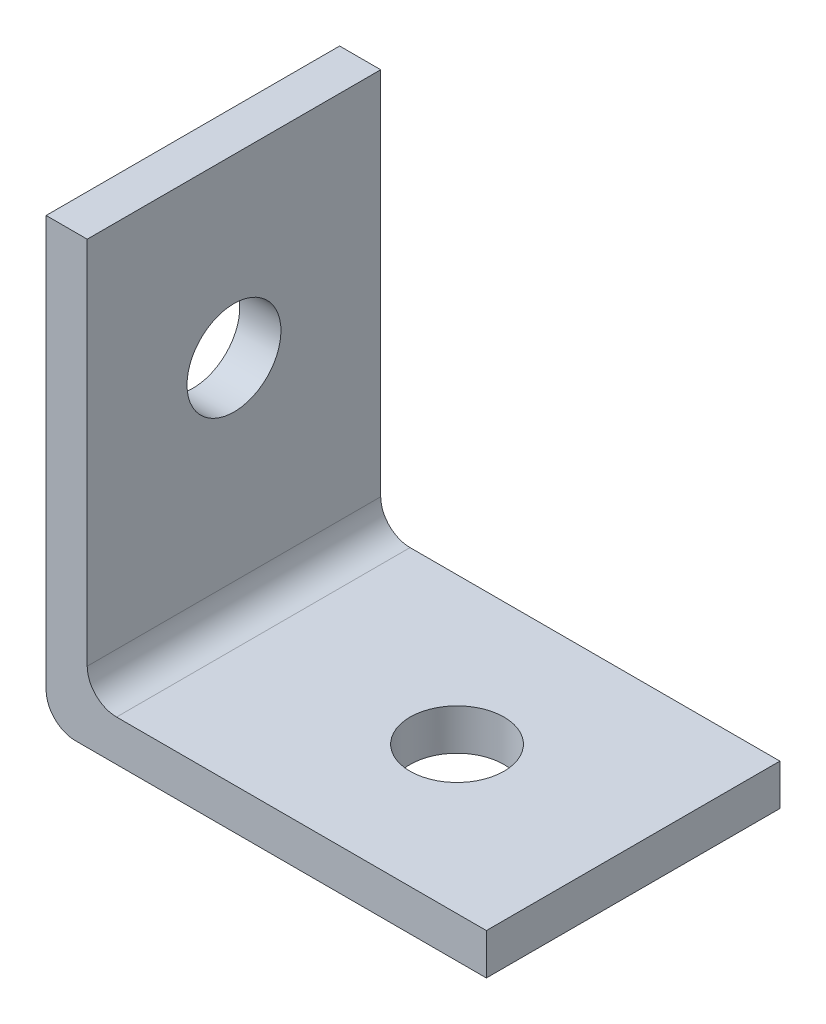
SolidWorks part; units mm, degrees
ref_plane "Front Plane" through (0, 0, 0) normal (0, 0, 1) x (1, 0, 0)
ref_plane "Top Plane" through (0, 0, 0) normal (0, 1, 0) x (1, 0, 0)
ref_plane "Right Plane" through (0, 0, 0) normal (1, 0, 0) x (0, 0, -1)
sketch "Sketch1" plane through (0, 0, 0) normal (0, 0, 1) x (1, 0, 0)
  line L0 (0, 0) -> (0, 19.05)
  line L1 (0, 19.05) -> (1.778, 19.05)
  line L2 (1.778, 19.05) -> (1.778, 1.778)
  line L3 (1.778, 1.778) -> (19.05, 1.778)
  line L4 (19.05, 1.778) -> (19.05, 0)
  line L5 (19.05, 0) -> (0, 0)
  dimension "D1" = 1.778
  dimension "D2" = 1.778
  dimension "D3" = 19.05
  dimension "D4" = 19.05
extrude "Boss-Extrude1" add sketch "Sketch1" against normal mid plane 12.7
sketch "Sketch2" plane through (0, 0, 0) normal (-1, 0, 0) x (0, 0, 1)
  line L0 (-6.35, 19.05) -> (6.35, 19.05) construction
  circle A0 centre (0, 11.43) radius 2.032
  point P2 (0, 0)
  dimension "D1" = 4.064
  dimension "D3" = 7.62
  dimension "D2" = 11.43
extrude "Cut-Extrude1" cut sketch "Sketch2" against normal up to next
sketch "Sketch3" plane through (0, 0, 0) normal (0, -1, 0) x (1, 0, 0)
  circle A0 centre (11.43, 0) radius 2.032
  point P5 (-0.9882, 0.9526)
  dimension "D1" = 4.064
  dimension "D2" = 11.43
extrude "Cut-Extrude2" cut sketch "Sketch3" against normal up to next
fillet "Fillet2" radius 1.27 1 edges at (1.778, 1.778, 0)
fillet "Fillet3" radius 1.27 1 edges at (0, 0, 0)
